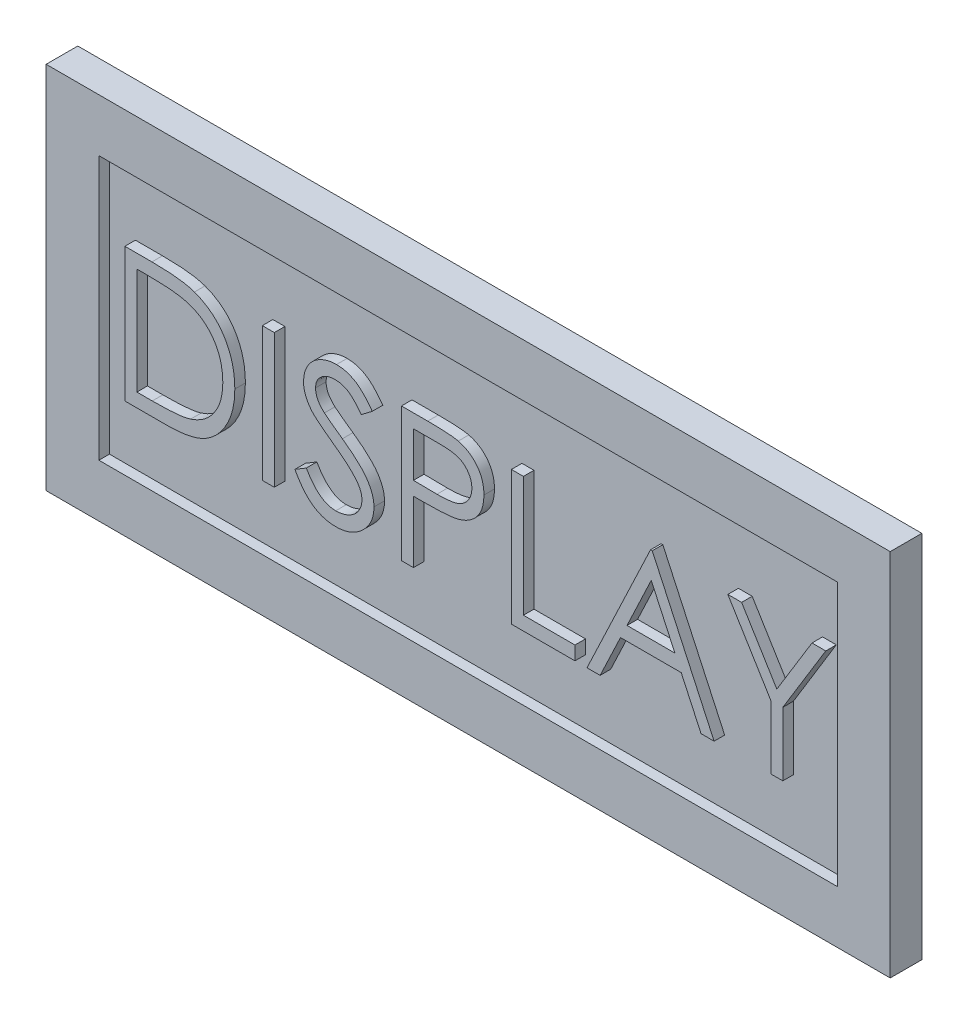
SolidWorks part; units mm, degrees
note: The reader was unsure of these and kept them because the rebuilt part matched: shared geometry of "스케치1<4>", "스케치1<5>".
ref_plane "정면" through (0, 0, 0) normal (0, 0, 1) x (1, 0, 0)
ref_plane "윗면" through (0, 0, 0) normal (0, 1, 0) x (1, 0, 0)
ref_plane "우측면" through (0, 0, 0) normal (1, 0, 0) x (0, 0, -1)
sketch "스케치1" plane through (0, 0, 0) normal (0, 0, 1) x (1, 0, 0)
  line L1 (0, 0) -> (80, 0)
  line L2 (0, 0) -> (0, -35)
  line L3 (0, -35) -> (80, -35)
  line L4 (80, 0) -> (80, -35)
  line L5 (5, -5) -> (75, -5)
  line L6 (5, -5) -> (5, -30)
  line L7 (5, -30) -> (75, -30)
  line L8 (75, -5) -> (75, -30)
  text T0 "<b>DISPLAY</b>" font "Century Gothic" height in points 48
  dimension "D1" = 80
  dimension "D2" = 35
  dimension "D3" = 5
  dimension "D4" = 5
  dimension "D5" = 5
  dimension "D6" = 5
extrude "보스-돌출1" add sketch "스케치1" along normal blind 3 contours L4 L1 L2 L3 L5 L8 L7 L6
extrude "컷-돌출1" cut sketch "스케치1<4>" along normal through all contours L8 L5 L6 L7
sketch "스케치1<4>" plane through (0, 0, 0) normal (0, 0, 1) x (1, 0, 0) same geometry as "스케치1"
extrude "보스-돌출2" add sketch "스케치1<5>" along normal blind 2 contours L8 L5 L6 L7
sketch "스케치1<5>" plane through (0, 0, 0) normal (0, 0, 1) x (1, 0, 0) same geometry as "스케치1"
sketch "스케치7" plane through (0, 0, 0) normal (0, 0, -1) x (-1, 0, 0)
sketch "스케치8" plane through (0, 0, 2) normal (0, 0, 1) x (1, 0, 0)
  text T0 "DISPLAY" font "Century Gothic" height in points 48
extrude "보스-돌출3" add sketch "스케치8" along normal blind 1
